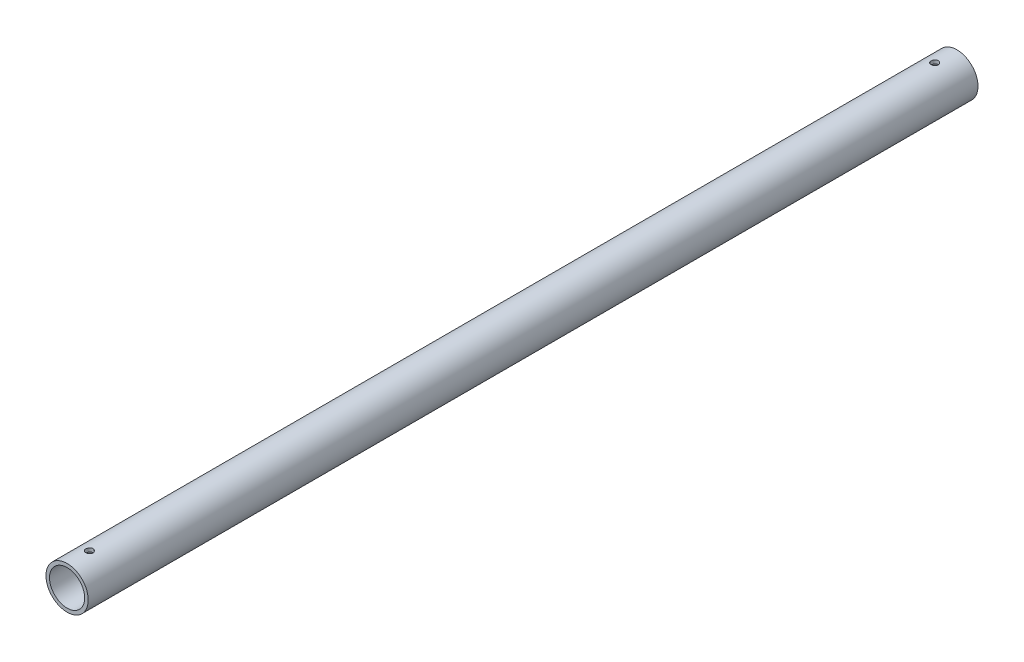
SolidWorks part; units mm, degrees
ref_plane "Front Plane" through (0, 0, 0) normal (0, 0, 1) x (1, 0, 0)
ref_plane "Top Plane" through (0, 0, 0) normal (0, 1, 0) x (1, 0, 0)
ref_plane "Right Plane" through (0, 0, 0) normal (1, 0, 0) x (0, 0, -1)
sketch "Sketch1" plane through (0, 0, 0) normal (0, 0, 1) x (1, 0, 0)
  circle A0 centre (0, 0) radius 9.5
  circle A1 centre (0, 0) radius 7.9
  dimension "D1" = 19
  dimension "D2" = 15.8
extrude "Boss-Extrude1" add sketch "Sketch1" along normal blind 400
sketch "Sketch2" plane through (0, 0, 0) normal (0, 1, 0) x (1, 0, 0)
  line L0 (7.9, 0) -> (-7.9, 0) construction
  line L1 (-9.5, -200) -> (9.5, -200)
  line L2 (-9.5, 0) -> (-9.5, -400) construction
  line L3 (9.5, -400) -> (9.5, 0) construction
  circle A0 centre (0, -10) radius 1.6
  circle A1 centre (0, -390) radius 1.6
  dimension "D1" = 3.2
  dimension "D2" = 10
extrude "Cut-Extrude1" cut sketch "Sketch2" against normal blind 400 and the other way blind 400 contours A0 | A1
